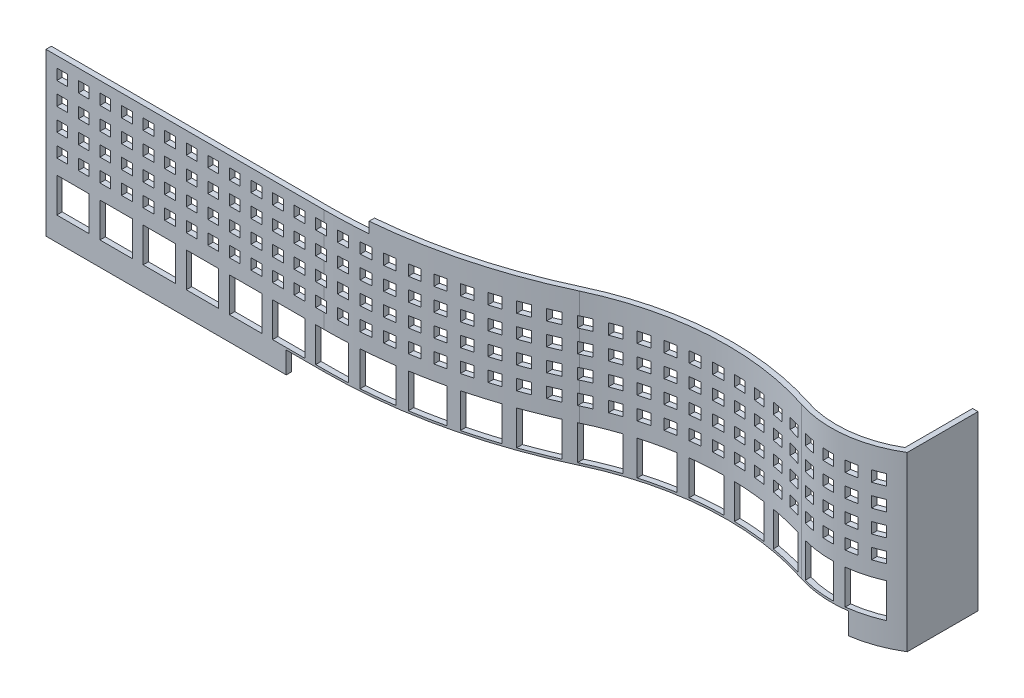
SolidWorks part; units mm, degrees
ref_plane "前视基准面" through (0, 0, 0) normal (0, 0, 1) x (1, 0, 0)
ref_plane "上视基准面" through (0, 0, 0) normal (0, 1, 0) x (1, 0, 0)
ref_plane "右视基准面" through (0, 0, 0) normal (1, 0, 0) x (0, 0, -1)
sketch "草图1" plane through (0, 0, 0) normal (0, 1, 0) x (1, 0, 0)
  line L0 (-20.7666, -25) -> (52, -25) construction
  line L1 (9, 56.2113) -> (9, -24.8219) construction
  line L2 (52, -25) -> (52, -18.6603) construction
  line L3 (52, -18.6603) -> (52, -12.3864)
  line L4 (5, -25) -> (-17.4714, -25)
  line L5 (52.5, -18.9443) -> (52.5, -12.3864)
  line L6 (5, -25.5) -> (-17.4714, -25.5)
  line L8 (52, -12.3864) -> (52.5, -12.3864)
  line L9 (-17.4714, -25) -> (-20.7666, -25)
  line L10 (-20.7666, -25) -> (-20.7666, -25.5)
  line L11 (-20.7666, -25.5) -> (-17.4714, -25.5)
  arc A0 (9, 31.229) -> (-20.7666, -25) centre (0, 0) ccw construction
  arc A1 (9, 29.1419) -> (-17.4714, -25) centre (0, 0) ccw construction
  circle A2 centre (0, 0) radius 32.5 construction
  circle A3 centre (0, 0) radius 30.5 construction
  arc A7 (43.892, -19.5048) -> (52, -18.6603) centre (47, -10) ccw
  arc A8 (43.892, -19.5048) -> (24.144, -20.7248) centre (35.5554, -45) ccw
  arc A9 (5, -25) -> (24.144, -20.7248) centre (5, 20) ccw
  arc A10 (43.7367, -19.98) -> (52.5, -18.9443) centre (47, -10) ccw
  arc A11 (43.7367, -19.98) -> (24.3567, -21.1773) centre (35.5554, -45) ccw
  arc A12 (5, -25.5) -> (24.3567, -21.1773) centre (5, 20) ccw
  dimension "D1" = 65
  dimension "D9" = 0.5
  dimension "D2" = 25
  dimension "D4" = 9
  dimension "D5" = 10
  dimension "D6" = 47
  dimension "D7" = 20
  dimension "D8" = 5
  dimension "D10" = 45
  dimension "D11" = 43
  dimension "D3" = 2
extrude "凸台-拉伸1" add sketch "草图1" along normal blind 16
sketch "草图2" plane through (0, 0, 25.5) normal (0, 0, 1) x (1, 0, 0)
  line L6 (-20.7666, 16) -> (9, 16)
  line L7 (24.3567, 16) -> (5, 16) construction
  line L8 (9, 16) -> (9, 15)
  line L9 (9, 15) -> (-20.7666, 15)
  line L10 (-20.7666, 16) -> (-20.7666, 0) construction
  line L11 (-20.7666, 15) -> (-20.7666, 16)
  dimension "D1" = 9
  dimension "D2" = 1
extrude "切除-拉伸1" cut sketch "草图2" against normal blind 15
sketch "草图3" plane through (0, 0, 0) normal (0, 0, 1) x (1, 0, 0)
  line L0 (48.2334, 14) -> (48.2334, 13)
  line L1 (-19.7666, 14) -> (-18.7666, 14)
  line L2 (-19.7666, 14) -> (-19.7666, 13)
  line L3 (-19.7666, 13) -> (-18.7666, 13)
  line L4 (-18.7666, 14) -> (-18.7666, 13)
  line L5 (48.2334, 13) -> (49.2334, 13)
  line L6 (-17.7666, 14) -> (-17.7666, 13)
  line L7 (-17.7666, 14) -> (-16.7666, 14)
  line L8 (-16.7666, 14) -> (-16.7666, 13)
  line L9 (-17.7666, 13) -> (-16.7666, 13)
  line L10 (-15.7666, 14) -> (-15.7666, 13)
  line L11 (-15.7666, 14) -> (-14.7666, 14)
  line L12 (-14.7666, 14) -> (-14.7666, 13)
  line L13 (-15.7666, 13) -> (-14.7666, 13)
  line L14 (-13.7666, 14) -> (-13.7666, 13)
  line L15 (-13.7666, 14) -> (-12.7666, 14)
  line L16 (-12.7666, 14) -> (-12.7666, 13)
  line L17 (-13.7666, 13) -> (-12.7666, 13)
  line L18 (-11.7666, 14) -> (-11.7666, 13)
  line L19 (-11.7666, 14) -> (-10.7666, 14)
  line L20 (-10.7666, 14) -> (-10.7666, 13)
  line L21 (-11.7666, 13) -> (-10.7666, 13)
  line L22 (-9.7666, 14) -> (-9.7666, 13)
  line L23 (-9.7666, 14) -> (-8.7666, 14)
  line L24 (-8.7666, 14) -> (-8.7666, 13)
  line L25 (-9.7666, 13) -> (-8.7666, 13)
  line L26 (-7.7666, 14) -> (-7.7666, 13)
  line L27 (-7.7666, 14) -> (-6.7666, 14)
  line L28 (-6.7666, 14) -> (-6.7666, 13)
  line L29 (-7.7666, 13) -> (-6.7666, 13)
  line L30 (-5.7666, 14) -> (-5.7666, 13)
  line L31 (-5.7666, 14) -> (-4.7666, 14)
  line L32 (-4.7666, 14) -> (-4.7666, 13)
  line L33 (-5.7666, 13) -> (-4.7666, 13)
  line L34 (-3.7666, 14) -> (-3.7666, 13)
  line L35 (-3.7666, 14) -> (-2.7666, 14)
  line L36 (-2.7666, 14) -> (-2.7666, 13)
  line L37 (-3.7666, 13) -> (-2.7666, 13)
  line L38 (-1.7666, 14) -> (-1.7666, 13)
  line L39 (-1.7666, 14) -> (-0.7666, 14)
  line L40 (-0.7666, 14) -> (-0.7666, 13)
  line L41 (-1.7666, 13) -> (-0.7666, 13)
  line L42 (0.2334, 14) -> (0.2334, 13)
  line L43 (0.2334, 14) -> (1.2334, 14)
  line L44 (1.2334, 14) -> (1.2334, 13)
  line L45 (0.2334, 13) -> (1.2334, 13)
  line L46 (2.2334, 14) -> (2.2334, 13)
  line L47 (2.2334, 14) -> (3.2334, 14)
  line L48 (3.2334, 14) -> (3.2334, 13)
  line L49 (2.2334, 13) -> (3.2334, 13)
  line L50 (4.2334, 14) -> (4.2334, 13)
  line L51 (4.2334, 14) -> (5.2334, 14)
  line L52 (5.2334, 14) -> (5.2334, 13)
  line L53 (4.2334, 13) -> (5.2334, 13)
  line L54 (6.2334, 14) -> (6.2334, 13)
  line L55 (6.2334, 14) -> (7.2334, 14)
  line L56 (7.2334, 14) -> (7.2334, 13)
  line L57 (6.2334, 13) -> (7.2334, 13)
  line L58 (8.2334, 14) -> (8.2334, 13)
  line L59 (8.2334, 14) -> (9.2334, 14)
  line L60 (9.2334, 14) -> (9.2334, 13)
  line L61 (8.2334, 13) -> (9.2334, 13)
  line L62 (10.2334, 14) -> (10.2334, 13)
  line L63 (10.2334, 14) -> (11.2334, 14)
  line L64 (11.2334, 14) -> (11.2334, 13)
  line L65 (10.2334, 13) -> (11.2334, 13)
  line L66 (12.2334, 14) -> (12.2334, 13)
  line L67 (12.2334, 14) -> (13.2334, 14)
  line L68 (13.2334, 14) -> (13.2334, 13)
  line L69 (12.2334, 13) -> (13.2334, 13)
  line L70 (14.2334, 14) -> (14.2334, 13)
  line L71 (14.2334, 14) -> (15.2334, 14)
  line L72 (15.2334, 14) -> (15.2334, 13)
  line L73 (14.2334, 13) -> (15.2334, 13)
  line L74 (16.2334, 14) -> (16.2334, 13)
  line L75 (16.2334, 14) -> (17.2334, 14)
  line L76 (17.2334, 14) -> (17.2334, 13)
  line L77 (16.2334, 13) -> (17.2334, 13)
  line L78 (18.2334, 14) -> (18.2334, 13)
  line L79 (18.2334, 14) -> (19.2334, 14)
  line L80 (19.2334, 14) -> (19.2334, 13)
  line L81 (18.2334, 13) -> (19.2334, 13)
  line L82 (20.2334, 14) -> (20.2334, 13)
  line L83 (20.2334, 14) -> (21.2334, 14)
  line L84 (21.2334, 14) -> (21.2334, 13)
  line L85 (20.2334, 13) -> (21.2334, 13)
  line L86 (22.2334, 14) -> (22.2334, 13)
  line L87 (22.2334, 14) -> (23.2334, 14)
  line L88 (23.2334, 14) -> (23.2334, 13)
  line L89 (22.2334, 13) -> (23.2334, 13)
  line L90 (24.2334, 14) -> (24.2334, 13)
  line L91 (24.2334, 14) -> (25.2334, 14)
  line L92 (25.2334, 14) -> (25.2334, 13)
  line L93 (24.2334, 13) -> (25.2334, 13)
  line L94 (26.2334, 14) -> (26.2334, 13)
  line L95 (26.2334, 14) -> (27.2334, 14)
  line L96 (27.2334, 14) -> (27.2334, 13)
  line L97 (26.2334, 13) -> (27.2334, 13)
  line L98 (28.2334, 14) -> (28.2334, 13)
  line L99 (28.2334, 14) -> (29.2334, 14)
  line L100 (29.2334, 14) -> (29.2334, 13)
  line L101 (28.2334, 13) -> (29.2334, 13)
  line L102 (30.2334, 14) -> (30.2334, 13)
  line L103 (30.2334, 14) -> (31.2334, 14)
  line L104 (31.2334, 14) -> (31.2334, 13)
  line L105 (30.2334, 13) -> (31.2334, 13)
  line L106 (32.2334, 14) -> (32.2334, 13)
  line L107 (32.2334, 14) -> (33.2334, 14)
  line L108 (33.2334, 14) -> (33.2334, 13)
  line L109 (32.2334, 13) -> (33.2334, 13)
  line L110 (34.2334, 14) -> (34.2334, 13)
  line L111 (34.2334, 14) -> (35.2334, 14)
  line L112 (35.2334, 14) -> (35.2334, 13)
  line L113 (34.2334, 13) -> (35.2334, 13)
  line L114 (36.2334, 14) -> (36.2334, 13)
  line L115 (36.2334, 14) -> (37.2334, 14)
  line L116 (37.2334, 14) -> (37.2334, 13)
  line L117 (36.2334, 13) -> (37.2334, 13)
  line L118 (38.2334, 14) -> (38.2334, 13)
  line L119 (38.2334, 14) -> (39.2334, 14)
  line L120 (39.2334, 14) -> (39.2334, 13)
  line L121 (38.2334, 13) -> (39.2334, 13)
  line L122 (40.2334, 14) -> (40.2334, 13)
  line L123 (40.2334, 14) -> (41.2334, 14)
  line L124 (41.2334, 14) -> (41.2334, 13)
  line L125 (40.2334, 13) -> (41.2334, 13)
  line L126 (42.2334, 14) -> (42.2334, 13)
  line L127 (42.2334, 14) -> (43.2334, 14)
  line L128 (43.2334, 14) -> (43.2334, 13)
  line L129 (42.2334, 13) -> (43.2334, 13)
  line L130 (44.2334, 14) -> (44.2334, 13)
  line L131 (44.2334, 14) -> (45.2334, 14)
  line L132 (45.2334, 14) -> (45.2334, 13)
  line L133 (44.2334, 13) -> (45.2334, 13)
  line L134 (46.2334, 14) -> (46.2334, 13)
  line L135 (46.2334, 14) -> (47.2334, 14)
  line L136 (47.2334, 14) -> (47.2334, 13)
  line L137 (46.2334, 13) -> (47.2334, 13)
  line L138 (-19.7666, 11.925) -> (-19.7666, 10.925)
  line L139 (-19.7666, 11.925) -> (-18.7666, 11.925)
  line L140 (-18.7666, 11.925) -> (-18.7666, 10.925)
  line L141 (-19.7666, 10.925) -> (-18.7666, 10.925)
  line L142 (-17.7666, 11.925) -> (-17.7666, 10.925)
  line L143 (-17.7666, 10.925) -> (-16.7666, 10.925)
  line L144 (-16.7666, 11.925) -> (-16.7666, 10.925)
  line L145 (-17.7666, 11.925) -> (-16.7666, 11.925)
  line L146 (-15.7666, 11.925) -> (-15.7666, 10.925)
  line L147 (-15.7666, 10.925) -> (-14.7666, 10.925)
  line L148 (-14.7666, 11.925) -> (-14.7666, 10.925)
  line L149 (-15.7666, 11.925) -> (-14.7666, 11.925)
  line L150 (-13.7666, 11.925) -> (-13.7666, 10.925)
  line L151 (-13.7666, 10.925) -> (-12.7666, 10.925)
  line L152 (-12.7666, 11.925) -> (-12.7666, 10.925)
  line L153 (-13.7666, 11.925) -> (-12.7666, 11.925)
  line L154 (-11.7666, 11.925) -> (-11.7666, 10.925)
  line L155 (-11.7666, 10.925) -> (-10.7666, 10.925)
  line L156 (-10.7666, 11.925) -> (-10.7666, 10.925)
  line L157 (-11.7666, 11.925) -> (-10.7666, 11.925)
  line L158 (-9.7666, 11.925) -> (-9.7666, 10.925)
  line L159 (-9.7666, 10.925) -> (-8.7666, 10.925)
  line L160 (-8.7666, 11.925) -> (-8.7666, 10.925)
  line L161 (-9.7666, 11.925) -> (-8.7666, 11.925)
  line L162 (-7.7666, 11.925) -> (-7.7666, 10.925)
  line L163 (-7.7666, 10.925) -> (-6.7666, 10.925)
  line L164 (-6.7666, 11.925) -> (-6.7666, 10.925)
  line L165 (-7.7666, 11.925) -> (-6.7666, 11.925)
  line L166 (-5.7666, 11.925) -> (-5.7666, 10.925)
  line L167 (-5.7666, 10.925) -> (-4.7666, 10.925)
  line L168 (-4.7666, 11.925) -> (-4.7666, 10.925)
  line L169 (-5.7666, 11.925) -> (-4.7666, 11.925)
  line L170 (-3.7666, 11.925) -> (-3.7666, 10.925)
  line L171 (-3.7666, 10.925) -> (-2.7666, 10.925)
  line L172 (-2.7666, 11.925) -> (-2.7666, 10.925)
  line L173 (-3.7666, 11.925) -> (-2.7666, 11.925)
  line L174 (-1.7666, 11.925) -> (-1.7666, 10.925)
  line L175 (-1.7666, 10.925) -> (-0.7666, 10.925)
  line L176 (-0.7666, 11.925) -> (-0.7666, 10.925)
  line L177 (-1.7666, 11.925) -> (-0.7666, 11.925)
  line L178 (0.2334, 11.925) -> (0.2334, 10.925)
  line L179 (0.2334, 10.925) -> (1.2334, 10.925)
  line L180 (1.2334, 11.925) -> (1.2334, 10.925)
  line L181 (0.2334, 11.925) -> (1.2334, 11.925)
  line L182 (2.2334, 11.925) -> (2.2334, 10.925)
  line L183 (2.2334, 10.925) -> (3.2334, 10.925)
  line L184 (3.2334, 11.925) -> (3.2334, 10.925)
  line L185 (2.2334, 11.925) -> (3.2334, 11.925)
  line L186 (4.2334, 11.925) -> (4.2334, 10.925)
  line L187 (4.2334, 10.925) -> (5.2334, 10.925)
  line L188 (5.2334, 11.925) -> (5.2334, 10.925)
  line L189 (4.2334, 11.925) -> (5.2334, 11.925)
  line L190 (6.2334, 11.925) -> (6.2334, 10.925)
  line L191 (6.2334, 10.925) -> (7.2334, 10.925)
  line L192 (7.2334, 11.925) -> (7.2334, 10.925)
  line L193 (6.2334, 11.925) -> (7.2334, 11.925)
  line L194 (8.2334, 11.925) -> (8.2334, 10.925)
  line L195 (8.2334, 10.925) -> (9.2334, 10.925)
  line L196 (9.2334, 11.925) -> (9.2334, 10.925)
  line L197 (8.2334, 11.925) -> (9.2334, 11.925)
  line L198 (10.2334, 11.925) -> (10.2334, 10.925)
  line L199 (10.2334, 10.925) -> (11.2334, 10.925)
  line L200 (11.2334, 11.925) -> (11.2334, 10.925)
  line L201 (10.2334, 11.925) -> (11.2334, 11.925)
  line L202 (12.2334, 11.925) -> (12.2334, 10.925)
  line L203 (12.2334, 10.925) -> (13.2334, 10.925)
  line L204 (13.2334, 11.925) -> (13.2334, 10.925)
  line L205 (12.2334, 11.925) -> (13.2334, 11.925)
  line L206 (14.2334, 11.925) -> (14.2334, 10.925)
  line L207 (14.2334, 10.925) -> (15.2334, 10.925)
  line L208 (15.2334, 11.925) -> (15.2334, 10.925)
  line L209 (14.2334, 11.925) -> (15.2334, 11.925)
  line L210 (16.2334, 11.925) -> (16.2334, 10.925)
  line L211 (16.2334, 10.925) -> (17.2334, 10.925)
  line L212 (17.2334, 11.925) -> (17.2334, 10.925)
  line L213 (16.2334, 11.925) -> (17.2334, 11.925)
  line L214 (18.2334, 11.925) -> (18.2334, 10.925)
  line L215 (18.2334, 10.925) -> (19.2334, 10.925)
  line L216 (19.2334, 11.925) -> (19.2334, 10.925)
  line L217 (18.2334, 11.925) -> (19.2334, 11.925)
  line L218 (20.2334, 11.925) -> (20.2334, 10.925)
  line L219 (20.2334, 10.925) -> (21.2334, 10.925)
  line L220 (21.2334, 11.925) -> (21.2334, 10.925)
  line L221 (20.2334, 11.925) -> (21.2334, 11.925)
  line L222 (22.2334, 11.925) -> (22.2334, 10.925)
  line L223 (22.2334, 10.925) -> (23.2334, 10.925)
  line L224 (23.2334, 11.925) -> (23.2334, 10.925)
  line L225 (22.2334, 11.925) -> (23.2334, 11.925)
  line L226 (24.2334, 11.925) -> (24.2334, 10.925)
  line L227 (24.2334, 10.925) -> (25.2334, 10.925)
  line L228 (25.2334, 11.925) -> (25.2334, 10.925)
  line L229 (24.2334, 11.925) -> (25.2334, 11.925)
  line L230 (26.2334, 11.925) -> (26.2334, 10.925)
  line L231 (26.2334, 10.925) -> (27.2334, 10.925)
  line L232 (27.2334, 11.925) -> (27.2334, 10.925)
  line L233 (26.2334, 11.925) -> (27.2334, 11.925)
  line L234 (28.2334, 11.925) -> (28.2334, 10.925)
  line L235 (28.2334, 10.925) -> (29.2334, 10.925)
  line L236 (29.2334, 11.925) -> (29.2334, 10.925)
  line L237 (28.2334, 11.925) -> (29.2334, 11.925)
  line L238 (30.2334, 11.925) -> (30.2334, 10.925)
  line L239 (30.2334, 10.925) -> (31.2334, 10.925)
  line L240 (31.2334, 11.925) -> (31.2334, 10.925)
  line L241 (30.2334, 11.925) -> (31.2334, 11.925)
  line L242 (32.2334, 11.925) -> (32.2334, 10.925)
  line L243 (32.2334, 10.925) -> (33.2334, 10.925)
  line L244 (33.2334, 11.925) -> (33.2334, 10.925)
  line L245 (32.2334, 11.925) -> (33.2334, 11.925)
  line L246 (34.2334, 11.925) -> (34.2334, 10.925)
  line L247 (34.2334, 10.925) -> (35.2334, 10.925)
  line L248 (35.2334, 11.925) -> (35.2334, 10.925)
  line L249 (34.2334, 11.925) -> (35.2334, 11.925)
  line L250 (36.2334, 11.925) -> (36.2334, 10.925)
  line L251 (36.2334, 10.925) -> (37.2334, 10.925)
  line L252 (37.2334, 11.925) -> (37.2334, 10.925)
  line L253 (36.2334, 11.925) -> (37.2334, 11.925)
  line L254 (38.2334, 11.925) -> (38.2334, 10.925)
  line L255 (38.2334, 10.925) -> (39.2334, 10.925)
  line L256 (39.2334, 11.925) -> (39.2334, 10.925)
  line L257 (38.2334, 11.925) -> (39.2334, 11.925)
  line L258 (40.2334, 11.925) -> (40.2334, 10.925)
  line L259 (40.2334, 10.925) -> (41.2334, 10.925)
  line L260 (41.2334, 11.925) -> (41.2334, 10.925)
  line L261 (40.2334, 11.925) -> (41.2334, 11.925)
  line L262 (42.2334, 11.925) -> (42.2334, 10.925)
  line L263 (42.2334, 10.925) -> (43.2334, 10.925)
  line L264 (43.2334, 11.925) -> (43.2334, 10.925)
  line L265 (42.2334, 11.925) -> (43.2334, 11.925)
  line L266 (44.2334, 11.925) -> (44.2334, 10.925)
  line L267 (44.2334, 10.925) -> (45.2334, 10.925)
  line L268 (45.2334, 11.925) -> (45.2334, 10.925)
  line L269 (44.2334, 11.925) -> (45.2334, 11.925)
  line L270 (46.2334, 11.925) -> (46.2334, 10.925)
  line L271 (46.2334, 10.925) -> (47.2334, 10.925)
  line L272 (47.2334, 11.925) -> (47.2334, 10.925)
  line L273 (46.2334, 11.925) -> (47.2334, 11.925)
  line L274 (-19.7666, 9.85) -> (-19.7666, 8.85)
  line L275 (-19.7666, 9.85) -> (-18.7666, 9.85)
  line L276 (-18.7666, 9.85) -> (-18.7666, 8.85)
  line L277 (-19.7666, 8.85) -> (-18.7666, 8.85)
  line L278 (-17.7666, 9.85) -> (-17.7666, 8.85)
  line L279 (-17.7666, 8.85) -> (-16.7666, 8.85)
  line L280 (-16.7666, 9.85) -> (-16.7666, 8.85)
  line L281 (-17.7666, 9.85) -> (-16.7666, 9.85)
  line L282 (-15.7666, 9.85) -> (-15.7666, 8.85)
  line L283 (-15.7666, 8.85) -> (-14.7666, 8.85)
  line L284 (-14.7666, 9.85) -> (-14.7666, 8.85)
  line L285 (-15.7666, 9.85) -> (-14.7666, 9.85)
  line L286 (-13.7666, 9.85) -> (-13.7666, 8.85)
  line L287 (-13.7666, 8.85) -> (-12.7666, 8.85)
  line L288 (-12.7666, 9.85) -> (-12.7666, 8.85)
  line L289 (-13.7666, 9.85) -> (-12.7666, 9.85)
  line L290 (-11.7666, 9.85) -> (-11.7666, 8.85)
  line L291 (-11.7666, 8.85) -> (-10.7666, 8.85)
  line L292 (-10.7666, 9.85) -> (-10.7666, 8.85)
  line L293 (-11.7666, 9.85) -> (-10.7666, 9.85)
  line L294 (-9.7666, 9.85) -> (-9.7666, 8.85)
  line L295 (-9.7666, 8.85) -> (-8.7666, 8.85)
  line L296 (-8.7666, 9.85) -> (-8.7666, 8.85)
  line L297 (-9.7666, 9.85) -> (-8.7666, 9.85)
  line L298 (-7.7666, 9.85) -> (-7.7666, 8.85)
  line L299 (-7.7666, 8.85) -> (-6.7666, 8.85)
  line L300 (-6.7666, 9.85) -> (-6.7666, 8.85)
  line L301 (-7.7666, 9.85) -> (-6.7666, 9.85)
  line L302 (-5.7666, 9.85) -> (-5.7666, 8.85)
  line L303 (-5.7666, 8.85) -> (-4.7666, 8.85)
  line L304 (-4.7666, 9.85) -> (-4.7666, 8.85)
  line L305 (-5.7666, 9.85) -> (-4.7666, 9.85)
  line L306 (-3.7666, 9.85) -> (-3.7666, 8.85)
  line L307 (-3.7666, 8.85) -> (-2.7666, 8.85)
  line L308 (-2.7666, 9.85) -> (-2.7666, 8.85)
  line L309 (-3.7666, 9.85) -> (-2.7666, 9.85)
  line L310 (-1.7666, 9.85) -> (-1.7666, 8.85)
  line L311 (-1.7666, 8.85) -> (-0.7666, 8.85)
  line L312 (-0.7666, 9.85) -> (-0.7666, 8.85)
  line L313 (-1.7666, 9.85) -> (-0.7666, 9.85)
  line L314 (0.2334, 9.85) -> (0.2334, 8.85)
  line L315 (0.2334, 8.85) -> (1.2334, 8.85)
  line L316 (1.2334, 9.85) -> (1.2334, 8.85)
  line L317 (0.2334, 9.85) -> (1.2334, 9.85)
  line L318 (2.2334, 9.85) -> (2.2334, 8.85)
  line L319 (2.2334, 8.85) -> (3.2334, 8.85)
  line L320 (3.2334, 9.85) -> (3.2334, 8.85)
  line L321 (2.2334, 9.85) -> (3.2334, 9.85)
  line L322 (4.2334, 9.85) -> (4.2334, 8.85)
  line L323 (4.2334, 8.85) -> (5.2334, 8.85)
  line L324 (5.2334, 9.85) -> (5.2334, 8.85)
  line L325 (4.2334, 9.85) -> (5.2334, 9.85)
  line L326 (6.2334, 9.85) -> (6.2334, 8.85)
  line L327 (6.2334, 8.85) -> (7.2334, 8.85)
  line L328 (7.2334, 9.85) -> (7.2334, 8.85)
  line L329 (6.2334, 9.85) -> (7.2334, 9.85)
  line L330 (8.2334, 9.85) -> (8.2334, 8.85)
  line L331 (8.2334, 8.85) -> (9.2334, 8.85)
  line L332 (9.2334, 9.85) -> (9.2334, 8.85)
  line L333 (8.2334, 9.85) -> (9.2334, 9.85)
  line L334 (10.2334, 9.85) -> (10.2334, 8.85)
  line L335 (10.2334, 8.85) -> (11.2334, 8.85)
  line L336 (11.2334, 9.85) -> (11.2334, 8.85)
  line L337 (10.2334, 9.85) -> (11.2334, 9.85)
  line L338 (12.2334, 9.85) -> (12.2334, 8.85)
  line L339 (12.2334, 8.85) -> (13.2334, 8.85)
  line L340 (13.2334, 9.85) -> (13.2334, 8.85)
  line L341 (12.2334, 9.85) -> (13.2334, 9.85)
  line L342 (14.2334, 9.85) -> (14.2334, 8.85)
  line L343 (14.2334, 8.85) -> (15.2334, 8.85)
  line L344 (15.2334, 9.85) -> (15.2334, 8.85)
  line L345 (14.2334, 9.85) -> (15.2334, 9.85)
  line L346 (16.2334, 9.85) -> (16.2334, 8.85)
  line L347 (16.2334, 8.85) -> (17.2334, 8.85)
  line L348 (17.2334, 9.85) -> (17.2334, 8.85)
  line L349 (16.2334, 9.85) -> (17.2334, 9.85)
  line L350 (18.2334, 9.85) -> (18.2334, 8.85)
  line L351 (18.2334, 8.85) -> (19.2334, 8.85)
  line L352 (19.2334, 9.85) -> (19.2334, 8.85)
  line L353 (18.2334, 9.85) -> (19.2334, 9.85)
  line L354 (20.2334, 9.85) -> (20.2334, 8.85)
  line L355 (20.2334, 8.85) -> (21.2334, 8.85)
  line L356 (21.2334, 9.85) -> (21.2334, 8.85)
  line L357 (20.2334, 9.85) -> (21.2334, 9.85)
  line L358 (22.2334, 9.85) -> (22.2334, 8.85)
  line L359 (22.2334, 8.85) -> (23.2334, 8.85)
  line L360 (23.2334, 9.85) -> (23.2334, 8.85)
  line L361 (22.2334, 9.85) -> (23.2334, 9.85)
  line L362 (24.2334, 9.85) -> (24.2334, 8.85)
  line L363 (24.2334, 8.85) -> (25.2334, 8.85)
  line L364 (25.2334, 9.85) -> (25.2334, 8.85)
  line L365 (24.2334, 9.85) -> (25.2334, 9.85)
  line L366 (26.2334, 9.85) -> (26.2334, 8.85)
  line L367 (26.2334, 8.85) -> (27.2334, 8.85)
  line L368 (27.2334, 9.85) -> (27.2334, 8.85)
  line L369 (26.2334, 9.85) -> (27.2334, 9.85)
  line L370 (28.2334, 9.85) -> (28.2334, 8.85)
  line L371 (28.2334, 8.85) -> (29.2334, 8.85)
  line L372 (29.2334, 9.85) -> (29.2334, 8.85)
  line L373 (28.2334, 9.85) -> (29.2334, 9.85)
  line L374 (30.2334, 9.85) -> (30.2334, 8.85)
  line L375 (30.2334, 8.85) -> (31.2334, 8.85)
  line L376 (31.2334, 9.85) -> (31.2334, 8.85)
  line L377 (30.2334, 9.85) -> (31.2334, 9.85)
  line L378 (32.2334, 9.85) -> (32.2334, 8.85)
  line L379 (32.2334, 8.85) -> (33.2334, 8.85)
  line L380 (33.2334, 9.85) -> (33.2334, 8.85)
  line L381 (32.2334, 9.85) -> (33.2334, 9.85)
  line L382 (34.2334, 9.85) -> (34.2334, 8.85)
  line L383 (34.2334, 8.85) -> (35.2334, 8.85)
  line L384 (35.2334, 9.85) -> (35.2334, 8.85)
  line L385 (34.2334, 9.85) -> (35.2334, 9.85)
  line L386 (36.2334, 9.85) -> (36.2334, 8.85)
  line L387 (36.2334, 8.85) -> (37.2334, 8.85)
  line L388 (37.2334, 9.85) -> (37.2334, 8.85)
  line L389 (36.2334, 9.85) -> (37.2334, 9.85)
  line L390 (38.2334, 9.85) -> (38.2334, 8.85)
  line L391 (38.2334, 8.85) -> (39.2334, 8.85)
  line L392 (39.2334, 9.85) -> (39.2334, 8.85)
  line L393 (38.2334, 9.85) -> (39.2334, 9.85)
  line L394 (40.2334, 9.85) -> (40.2334, 8.85)
  line L395 (40.2334, 8.85) -> (41.2334, 8.85)
  line L396 (41.2334, 9.85) -> (41.2334, 8.85)
  line L397 (40.2334, 9.85) -> (41.2334, 9.85)
  line L398 (42.2334, 9.85) -> (42.2334, 8.85)
  line L399 (42.2334, 8.85) -> (43.2334, 8.85)
  line L400 (43.2334, 9.85) -> (43.2334, 8.85)
  line L401 (42.2334, 9.85) -> (43.2334, 9.85)
  line L402 (44.2334, 9.85) -> (44.2334, 8.85)
  line L403 (44.2334, 8.85) -> (45.2334, 8.85)
  line L404 (45.2334, 9.85) -> (45.2334, 8.85)
  line L405 (44.2334, 9.85) -> (45.2334, 9.85)
  line L406 (46.2334, 9.85) -> (46.2334, 8.85)
  line L407 (46.2334, 8.85) -> (47.2334, 8.85)
  line L408 (47.2334, 9.85) -> (47.2334, 8.85)
  line L409 (46.2334, 9.85) -> (47.2334, 9.85)
  line L410 (-19.7666, 7.775) -> (-19.7666, 6.775)
  line L411 (-19.7666, 7.775) -> (-18.7666, 7.775)
  line L412 (-18.7666, 7.775) -> (-18.7666, 6.775)
  line L413 (-19.7666, 6.775) -> (-18.7666, 6.775)
  line L414 (-17.7666, 7.775) -> (-17.7666, 6.775)
  line L415 (-17.7666, 6.775) -> (-16.7666, 6.775)
  line L416 (-16.7666, 7.775) -> (-16.7666, 6.775)
  line L417 (-17.7666, 7.775) -> (-16.7666, 7.775)
  line L418 (-15.7666, 7.775) -> (-15.7666, 6.775)
  line L419 (-15.7666, 6.775) -> (-14.7666, 6.775)
  line L420 (-14.7666, 7.775) -> (-14.7666, 6.775)
  line L421 (-15.7666, 7.775) -> (-14.7666, 7.775)
  line L422 (-13.7666, 7.775) -> (-13.7666, 6.775)
  line L423 (-13.7666, 6.775) -> (-12.7666, 6.775)
  line L424 (-12.7666, 7.775) -> (-12.7666, 6.775)
  line L425 (-13.7666, 7.775) -> (-12.7666, 7.775)
  line L426 (-11.7666, 7.775) -> (-11.7666, 6.775)
  line L427 (-11.7666, 6.775) -> (-10.7666, 6.775)
  line L428 (-10.7666, 7.775) -> (-10.7666, 6.775)
  line L429 (-11.7666, 7.775) -> (-10.7666, 7.775)
  line L430 (-9.7666, 7.775) -> (-9.7666, 6.775)
  line L431 (-9.7666, 6.775) -> (-8.7666, 6.775)
  line L432 (-8.7666, 7.775) -> (-8.7666, 6.775)
  line L433 (-9.7666, 7.775) -> (-8.7666, 7.775)
  line L434 (-7.7666, 7.775) -> (-7.7666, 6.775)
  line L435 (-7.7666, 6.775) -> (-6.7666, 6.775)
  line L436 (-6.7666, 7.775) -> (-6.7666, 6.775)
  line L437 (-7.7666, 7.775) -> (-6.7666, 7.775)
  line L438 (-5.7666, 7.775) -> (-5.7666, 6.775)
  line L439 (-5.7666, 6.775) -> (-4.7666, 6.775)
  line L440 (-4.7666, 7.775) -> (-4.7666, 6.775)
  line L441 (-5.7666, 7.775) -> (-4.7666, 7.775)
  line L442 (-3.7666, 7.775) -> (-3.7666, 6.775)
  line L443 (-3.7666, 6.775) -> (-2.7666, 6.775)
  line L444 (-2.7666, 7.775) -> (-2.7666, 6.775)
  line L445 (-3.7666, 7.775) -> (-2.7666, 7.775)
  line L446 (-1.7666, 7.775) -> (-1.7666, 6.775)
  line L447 (-1.7666, 6.775) -> (-0.7666, 6.775)
  line L448 (-0.7666, 7.775) -> (-0.7666, 6.775)
  line L449 (-1.7666, 7.775) -> (-0.7666, 7.775)
  line L450 (0.2334, 7.775) -> (0.2334, 6.775)
  line L451 (0.2334, 6.775) -> (1.2334, 6.775)
  line L452 (1.2334, 7.775) -> (1.2334, 6.775)
  line L453 (0.2334, 7.775) -> (1.2334, 7.775)
  line L454 (2.2334, 7.775) -> (2.2334, 6.775)
  line L455 (2.2334, 6.775) -> (3.2334, 6.775)
  line L456 (3.2334, 7.775) -> (3.2334, 6.775)
  line L457 (2.2334, 7.775) -> (3.2334, 7.775)
  line L458 (4.2334, 7.775) -> (4.2334, 6.775)
  line L459 (4.2334, 6.775) -> (5.2334, 6.775)
  line L460 (5.2334, 7.775) -> (5.2334, 6.775)
  line L461 (4.2334, 7.775) -> (5.2334, 7.775)
  line L462 (6.2334, 7.775) -> (6.2334, 6.775)
  line L463 (6.2334, 6.775) -> (7.2334, 6.775)
  line L464 (7.2334, 7.775) -> (7.2334, 6.775)
  line L465 (6.2334, 7.775) -> (7.2334, 7.775)
  line L466 (8.2334, 7.775) -> (8.2334, 6.775)
  line L467 (8.2334, 6.775) -> (9.2334, 6.775)
  line L468 (9.2334, 7.775) -> (9.2334, 6.775)
  line L469 (8.2334, 7.775) -> (9.2334, 7.775)
  line L470 (10.2334, 7.775) -> (10.2334, 6.775)
  line L471 (10.2334, 6.775) -> (11.2334, 6.775)
  line L472 (11.2334, 7.775) -> (11.2334, 6.775)
  line L473 (10.2334, 7.775) -> (11.2334, 7.775)
  line L474 (12.2334, 7.775) -> (12.2334, 6.775)
  line L475 (12.2334, 6.775) -> (13.2334, 6.775)
  line L476 (13.2334, 7.775) -> (13.2334, 6.775)
  line L477 (12.2334, 7.775) -> (13.2334, 7.775)
  line L478 (14.2334, 7.775) -> (14.2334, 6.775)
  line L479 (14.2334, 6.775) -> (15.2334, 6.775)
  line L480 (15.2334, 7.775) -> (15.2334, 6.775)
  line L481 (14.2334, 7.775) -> (15.2334, 7.775)
  line L482 (16.2334, 7.775) -> (16.2334, 6.775)
  line L483 (16.2334, 6.775) -> (17.2334, 6.775)
  line L484 (17.2334, 7.775) -> (17.2334, 6.775)
  line L485 (16.2334, 7.775) -> (17.2334, 7.775)
  line L486 (18.2334, 7.775) -> (18.2334, 6.775)
  line L487 (18.2334, 6.775) -> (19.2334, 6.775)
  line L488 (19.2334, 7.775) -> (19.2334, 6.775)
  line L489 (18.2334, 7.775) -> (19.2334, 7.775)
  line L490 (20.2334, 7.775) -> (20.2334, 6.775)
  line L491 (20.2334, 6.775) -> (21.2334, 6.775)
  line L492 (21.2334, 7.775) -> (21.2334, 6.775)
  line L493 (20.2334, 7.775) -> (21.2334, 7.775)
  line L494 (22.2334, 7.775) -> (22.2334, 6.775)
  line L495 (22.2334, 6.775) -> (23.2334, 6.775)
  line L496 (23.2334, 7.775) -> (23.2334, 6.775)
  line L497 (22.2334, 7.775) -> (23.2334, 7.775)
  line L498 (24.2334, 7.775) -> (24.2334, 6.775)
  line L499 (24.2334, 6.775) -> (25.2334, 6.775)
  line L500 (25.2334, 7.775) -> (25.2334, 6.775)
  line L501 (24.2334, 7.775) -> (25.2334, 7.775)
  line L502 (26.2334, 7.775) -> (26.2334, 6.775)
  line L503 (26.2334, 6.775) -> (27.2334, 6.775)
  line L504 (27.2334, 7.775) -> (27.2334, 6.775)
  line L505 (26.2334, 7.775) -> (27.2334, 7.775)
  line L506 (28.2334, 7.775) -> (28.2334, 6.775)
  line L507 (28.2334, 6.775) -> (29.2334, 6.775)
  line L508 (29.2334, 7.775) -> (29.2334, 6.775)
  line L509 (28.2334, 7.775) -> (29.2334, 7.775)
  line L510 (30.2334, 7.775) -> (30.2334, 6.775)
  line L511 (30.2334, 6.775) -> (31.2334, 6.775)
  line L512 (31.2334, 7.775) -> (31.2334, 6.775)
  line L513 (30.2334, 7.775) -> (31.2334, 7.775)
  line L514 (32.2334, 7.775) -> (32.2334, 6.775)
  line L515 (32.2334, 6.775) -> (33.2334, 6.775)
  line L516 (33.2334, 7.775) -> (33.2334, 6.775)
  line L517 (32.2334, 7.775) -> (33.2334, 7.775)
  line L518 (34.2334, 7.775) -> (34.2334, 6.775)
  line L519 (34.2334, 6.775) -> (35.2334, 6.775)
  line L520 (35.2334, 7.775) -> (35.2334, 6.775)
  line L521 (34.2334, 7.775) -> (35.2334, 7.775)
  line L522 (36.2334, 7.775) -> (36.2334, 6.775)
  line L523 (36.2334, 6.775) -> (37.2334, 6.775)
  line L524 (37.2334, 7.775) -> (37.2334, 6.775)
  line L525 (36.2334, 7.775) -> (37.2334, 7.775)
  line L526 (38.2334, 7.775) -> (38.2334, 6.775)
  line L527 (38.2334, 6.775) -> (39.2334, 6.775)
  line L528 (39.2334, 7.775) -> (39.2334, 6.775)
  line L529 (38.2334, 7.775) -> (39.2334, 7.775)
  line L530 (40.2334, 7.775) -> (40.2334, 6.775)
  line L531 (40.2334, 6.775) -> (41.2334, 6.775)
  line L532 (41.2334, 7.775) -> (41.2334, 6.775)
  line L533 (40.2334, 7.775) -> (41.2334, 7.775)
  line L534 (42.2334, 7.775) -> (42.2334, 6.775)
  line L535 (42.2334, 6.775) -> (43.2334, 6.775)
  line L536 (43.2334, 7.775) -> (43.2334, 6.775)
  line L537 (42.2334, 7.775) -> (43.2334, 7.775)
  line L538 (44.2334, 7.775) -> (44.2334, 6.775)
  line L539 (44.2334, 6.775) -> (45.2334, 6.775)
  line L540 (45.2334, 7.775) -> (45.2334, 6.775)
  line L541 (44.2334, 7.775) -> (45.2334, 7.775)
  line L542 (46.2334, 7.775) -> (46.2334, 6.775)
  line L543 (46.2334, 6.775) -> (47.2334, 6.775)
  line L544 (47.2334, 7.775) -> (47.2334, 6.775)
  line L545 (46.2334, 7.775) -> (47.2334, 7.775)
  line L682 (-20.7666, 0) -> (5, 0) construction
  line L683 (-19.7666, 5.4) -> (-16.7666, 5.4)
  line L684 (-19.7666, 5.4) -> (-19.7666, 2.2)
  line L685 (-19.7666, 2.2) -> (-16.7666, 2.2)
  line L686 (-16.7666, 5.4) -> (-16.7666, 2.2)
  line L687 (-15.7666, 5.4) -> (-15.7666, 2.2)
  line L688 (-15.7666, 5.4) -> (-12.7666, 5.4)
  line L689 (-12.7666, 5.4) -> (-12.7666, 2.2)
  line L690 (-15.7666, 2.2) -> (-12.7666, 2.2)
  line L691 (-11.7666, 5.4) -> (-11.7666, 2.2)
  line L692 (-11.7666, 5.4) -> (-8.7666, 5.4)
  line L693 (-8.7666, 5.4) -> (-8.7666, 2.2)
  line L694 (-11.7666, 2.2) -> (-8.7666, 2.2)
  line L695 (-7.7666, 5.4) -> (-7.7666, 2.2)
  line L696 (-7.7666, 5.4) -> (-4.7666, 5.4)
  line L697 (-4.7666, 5.4) -> (-4.7666, 2.2)
  line L698 (-7.7666, 2.2) -> (-4.7666, 2.2)
  line L699 (-3.7666, 5.4) -> (-3.7666, 2.2)
  line L700 (-3.7666, 5.4) -> (-0.7666, 5.4)
  line L701 (-0.7666, 5.4) -> (-0.7666, 2.2)
  line L702 (-3.7666, 2.2) -> (-0.7666, 2.2)
  line L703 (0.2334, 5.4) -> (0.2334, 2.2)
  line L704 (0.2334, 5.4) -> (3.2334, 5.4)
  line L705 (3.2334, 5.4) -> (3.2334, 2.2)
  line L706 (0.2334, 2.2) -> (3.2334, 2.2)
  line L707 (4.2334, 5.4) -> (4.2334, 2.2)
  line L708 (4.2334, 5.4) -> (7.2334, 5.4)
  line L709 (7.2334, 5.4) -> (7.2334, 2.2)
  line L710 (4.2334, 2.2) -> (7.2334, 2.2)
  line L711 (8.2334, 5.4) -> (8.2334, 2.2)
  line L712 (8.2334, 5.4) -> (11.2334, 5.4)
  line L713 (11.2334, 5.4) -> (11.2334, 2.2)
  line L714 (8.2334, 2.2) -> (11.2334, 2.2)
  line L715 (12.2334, 5.4) -> (12.2334, 2.2)
  line L716 (12.2334, 5.4) -> (15.2334, 5.4)
  line L717 (15.2334, 5.4) -> (15.2334, 2.2)
  line L718 (12.2334, 2.2) -> (15.2334, 2.2)
  line L719 (16.2334, 5.4) -> (16.2334, 2.2)
  line L720 (16.2334, 5.4) -> (19.2334, 5.4)
  line L721 (19.2334, 5.4) -> (19.2334, 2.2)
  line L722 (16.2334, 2.2) -> (19.2334, 2.2)
  line L723 (20.2334, 5.4) -> (20.2334, 2.2)
  line L724 (20.2334, 5.4) -> (23.2334, 5.4)
  line L725 (23.2334, 5.4) -> (23.2334, 2.2)
  line L726 (20.2334, 2.2) -> (23.2334, 2.2)
  line L727 (24.2334, 5.4) -> (24.2334, 2.2)
  line L728 (24.2334, 5.4) -> (27.2334, 5.4)
  line L729 (27.2334, 5.4) -> (27.2334, 2.2)
  line L730 (24.2334, 2.2) -> (27.2334, 2.2)
  line L731 (28.2334, 5.4) -> (28.2334, 2.2)
  line L732 (28.2334, 5.4) -> (31.2334, 5.4)
  line L733 (31.2334, 5.4) -> (31.2334, 2.2)
  line L734 (28.2334, 2.2) -> (31.2334, 2.2)
  line L735 (32.2334, 5.4) -> (32.2334, 2.2)
  line L736 (32.2334, 5.4) -> (35.2334, 5.4)
  line L737 (35.2334, 5.4) -> (35.2334, 2.2)
  line L738 (32.2334, 2.2) -> (35.2334, 2.2)
  line L739 (36.2334, 5.4) -> (36.2334, 2.2)
  line L740 (36.2334, 5.4) -> (39.2334, 5.4)
  line L741 (39.2334, 5.4) -> (39.2334, 2.2)
  line L742 (36.2334, 2.2) -> (39.2334, 2.2)
  line L743 (40.2334, 5.4) -> (40.2334, 2.2)
  line L744 (40.2334, 5.4) -> (43.2334, 5.4)
  line L745 (43.2334, 5.4) -> (43.2334, 2.2)
  line L746 (40.2334, 2.2) -> (43.2334, 2.2)
  line L747 (44.2334, 5.4) -> (44.2334, 2.2)
  line L748 (44.2334, 5.4) -> (47.2334, 5.4)
  line L749 (47.2334, 5.4) -> (47.2334, 2.2)
  line L750 (44.2334, 2.2) -> (47.2334, 2.2)
  line L751 (-20.7666, 15) -> (-20.7666, 0) construction
  line L752 (-20.7666, 15) -> (5, 15) construction
  line L753 (-19.7666, 5.7) -> (-19.7666, 4.7) [skipped]
  line L754 (-18.7666, 5.7) -> (-18.7666, 4.7) [skipped]
  line L755 (-17.7666, 5.7) -> (-17.7666, 4.7) [skipped]
  line L756 (-16.7666, 5.7) -> (-16.7666, 4.7) [skipped]
  line L757 (-15.7666, 5.7) -> (-15.7666, 4.7) [skipped]
  line L758 (-14.7666, 5.7) -> (-14.7666, 4.7) [skipped]
  line L759 (-13.7666, 5.7) -> (-13.7666, 4.7) [skipped]
  line L760 (-12.7666, 5.7) -> (-12.7666, 4.7) [skipped]
  line L761 (-11.7666, 5.7) -> (-11.7666, 4.7) [skipped]
  line L762 (-10.7666, 5.7) -> (-10.7666, 4.7) [skipped]
  line L763 (-9.7666, 5.7) -> (-9.7666, 4.7) [skipped]
  line L764 (-8.7666, 5.7) -> (-8.7666, 4.7) [skipped]
  line L765 (-7.7666, 5.7) -> (-7.7666, 4.7) [skipped]
  line L766 (-6.7666, 5.7) -> (-6.7666, 4.7) [skipped]
  line L767 (-5.7666, 5.7) -> (-5.7666, 4.7) [skipped]
  line L768 (-4.7666, 5.7) -> (-4.7666, 4.7) [skipped]
  line L769 (-3.7666, 5.7) -> (-3.7666, 4.7) [skipped]
  line L770 (-2.7666, 5.7) -> (-2.7666, 4.7) [skipped]
  line L771 (-1.7666, 5.7) -> (-1.7666, 4.7) [skipped]
  line L772 (-0.7666, 5.7) -> (-0.7666, 4.7) [skipped]
  line L773 (0.2334, 5.7) -> (0.2334, 4.7) [skipped]
  line L774 (1.2334, 5.7) -> (1.2334, 4.7) [skipped]
  line L775 (2.2334, 5.7) -> (2.2334, 4.7) [skipped]
  line L776 (3.2334, 5.7) -> (3.2334, 4.7) [skipped]
  line L777 (4.2334, 5.7) -> (4.2334, 4.7) [skipped]
  line L778 (5.2334, 5.7) -> (5.2334, 4.7) [skipped]
  line L779 (6.2334, 5.7) -> (6.2334, 4.7) [skipped]
  line L780 (7.2334, 5.7) -> (7.2334, 4.7) [skipped]
  line L781 (8.2334, 5.7) -> (8.2334, 4.7) [skipped]
  line L782 (9.2334, 5.7) -> (9.2334, 4.7) [skipped]
  line L783 (10.2334, 5.7) -> (10.2334, 4.7) [skipped]
  line L784 (11.2334, 5.7) -> (11.2334, 4.7) [skipped]
  line L785 (12.2334, 5.7) -> (12.2334, 4.7) [skipped]
  line L786 (13.2334, 5.7) -> (13.2334, 4.7) [skipped]
  line L787 (14.2334, 5.7) -> (14.2334, 4.7) [skipped]
  line L788 (15.2334, 5.7) -> (15.2334, 4.7) [skipped]
  line L789 (16.2334, 5.7) -> (16.2334, 4.7) [skipped]
  line L790 (17.2334, 5.7) -> (17.2334, 4.7) [skipped]
  line L791 (18.2334, 5.7) -> (18.2334, 4.7) [skipped]
  line L792 (19.2334, 5.7) -> (19.2334, 4.7) [skipped]
  line L793 (20.2334, 5.7) -> (20.2334, 4.7) [skipped]
  line L794 (21.2334, 5.7) -> (21.2334, 4.7) [skipped]
  line L795 (22.2334, 5.7) -> (22.2334, 4.7) [skipped]
  line L796 (23.2334, 5.7) -> (23.2334, 4.7) [skipped]
  line L797 (24.2334, 5.7) -> (24.2334, 4.7) [skipped]
  line L798 (25.2334, 5.7) -> (25.2334, 4.7) [skipped]
  line L799 (26.2334, 5.7) -> (26.2334, 4.7) [skipped]
  line L800 (27.2334, 5.7) -> (27.2334, 4.7) [skipped]
  line L801 (28.2334, 5.7) -> (28.2334, 4.7) [skipped]
  line L802 (29.2334, 5.7) -> (29.2334, 4.7) [skipped]
  line L803 (30.2334, 5.7) -> (30.2334, 4.7) [skipped]
  line L804 (31.2334, 5.7) -> (31.2334, 4.7) [skipped]
  line L805 (32.2334, 5.7) -> (32.2334, 4.7) [skipped]
  line L806 (33.2334, 5.7) -> (33.2334, 4.7) [skipped]
  line L807 (34.2334, 5.7) -> (34.2334, 4.7) [skipped]
  line L808 (35.2334, 5.7) -> (35.2334, 4.7) [skipped]
  line L809 (36.2334, 5.7) -> (36.2334, 4.7) [skipped]
  line L810 (37.2334, 5.7) -> (37.2334, 4.7) [skipped]
  line L811 (38.2334, 5.7) -> (38.2334, 4.7) [skipped]
  line L812 (39.2334, 5.7) -> (39.2334, 4.7) [skipped]
  line L813 (40.2334, 5.7) -> (40.2334, 4.7) [skipped]
  line L814 (41.2334, 5.7) -> (41.2334, 4.7) [skipped]
  line L815 (42.2334, 5.7) -> (42.2334, 4.7) [skipped]
  line L816 (43.2334, 5.7) -> (43.2334, 4.7) [skipped]
  line L817 (44.2334, 5.7) -> (44.2334, 4.7) [skipped]
  line L818 (45.2334, 5.7) -> (45.2334, 4.7) [skipped]
  line L819 (46.2334, 5.7) -> (46.2334, 4.7) [skipped]
  line L820 (47.2334, 5.7) -> (47.2334, 4.7) [skipped]
  line L821 (46.2334, 5.7) -> (47.2334, 5.7) [skipped]
  line L822 (46.2334, 4.7) -> (47.2334, 4.7) [skipped]
  line L823 (44.2334, 4.7) -> (45.2334, 4.7) [skipped]
  line L824 (44.2334, 5.7) -> (45.2334, 5.7) [skipped]
  line L825 (42.2334, 4.7) -> (42.719, 4.7) [skipped]
  line L826 (42.2334, 5.7) -> (43.2334, 5.7) [skipped]
  line L827 (40.2334, 5.7) -> (41.2334, 5.7) [skipped]
  line L828 (40.2334, 4.7) -> (41.2334, 4.7) [skipped]
  line L829 (38.2334, 4.7) -> (39.2334, 4.7) [skipped]
  line L830 (38.2334, 5.7) -> (39.2334, 5.7) [skipped]
  line L831 (36.2334, 5.7) -> (37.2334, 5.7) [skipped]
  line L832 (36.2334, 4.7) -> (37.2334, 4.7) [skipped]
  line L833 (34.2334, 4.7) -> (35.2334, 4.7) [skipped]
  line L834 (34.2334, 5.7) -> (35.2334, 5.7) [skipped]
  line L835 (32.2334, 5.7) -> (33.2334, 5.7) [skipped]
  line L836 (32.2334, 4.7) -> (33.2334, 4.7) [skipped]
  line L837 (30.2334, 4.7) -> (31.2334, 4.7) [skipped]
  line L838 (30.2334, 5.7) -> (31.2334, 5.7) [skipped]
  line L839 (28.2334, 5.7) -> (29.2334, 5.7) [skipped]
  line L840 (28.2334, 4.7) -> (29.2334, 4.7) [skipped]
  line L841 (26.2334, 4.7) -> (27.2334, 4.7) [skipped]
  line L842 (26.2334, 5.7) -> (27.2334, 5.7) [skipped]
  line L843 (24.2334, 5.7) -> (25.2334, 5.7) [skipped]
  line L844 (24.2334, 4.7) -> (25.2334, 4.7) [skipped]
  line L845 (22.2334, 4.7) -> (23.2334, 4.7) [skipped]
  line L846 (22.2334, 5.7) -> (23.2334, 5.7) [skipped]
  line L847 (20.2334, 5.7) -> (21.2334, 5.7) [skipped]
  line L848 (20.2334, 4.7) -> (21.2334, 4.7) [skipped]
  line L849 (18.2334, 4.7) -> (19.2334, 4.7) [skipped]
  line L850 (18.2334, 5.7) -> (19.2334, 5.7) [skipped]
  line L851 (16.2334, 5.7) -> (17.2334, 5.7) [skipped]
  line L852 (16.2334, 4.7) -> (17.2334, 4.7) [skipped]
  line L853 (14.2334, 4.7) -> (15.2334, 4.7) [skipped]
  line L854 (14.2334, 5.7) -> (15.2334, 5.7) [skipped]
  line L855 (12.2334, 4.7) -> (13.2334, 4.7) [skipped]
  line L856 (12.2334, 5.7) -> (13.2334, 5.7) [skipped]
  line L857 (10.2334, 5.7) -> (11.2334, 5.7) [skipped]
  line L858 (10.2334, 4.7) -> (11.2334, 4.7) [skipped]
  line L859 (8.2334, 4.7) -> (9.2334, 4.7) [skipped]
  line L860 (8.2334, 5.7) -> (9.2334, 5.7) [skipped]
  line L861 (6.2334, 5.7) -> (7.2334, 5.7) [skipped]
  line L862 (6.2334, 4.7) -> (7.2334, 4.7) [skipped]
  line L863 (4.2334, 4.7) -> (5.2334, 4.7) [skipped]
  line L864 (4.2334, 5.7) -> (5.2334, 5.7) [skipped]
  line L865 (2.2334, 5.7) -> (3.2334, 5.7) [skipped]
  line L866 (2.2334, 4.7) -> (3.2334, 4.7) [skipped]
  line L867 (0.2334, 4.7) -> (1.2334, 4.7) [skipped]
  line L868 (-1.7666, 5.7) -> (-0.7666, 5.7) [skipped]
  line L869 (-1.7666, 4.7) -> (-0.7666, 4.7) [skipped]
  line L870 (0.2334, 5.7) -> (1.2334, 5.7) [skipped]
  line L871 (-3.7666, 5.7) -> (-2.7666, 5.7) [skipped]
  line L872 (-3.7666, 4.7) -> (-2.7666, 4.7) [skipped]
  line L873 (-5.7666, 4.7) -> (-4.7666, 4.7) [skipped]
  line L874 (-5.7666, 5.7) -> (-4.7666, 5.7) [skipped]
  line L875 (-7.7666, 5.7) -> (-6.7666, 5.7) [skipped]
  line L876 (-7.7666, 4.7) -> (-6.7666, 4.7) [skipped]
  line L877 (-9.7666, 4.7) -> (-8.7666, 4.7) [skipped]
  line L878 (-9.7666, 5.7) -> (-8.7666, 5.7) [skipped]
  line L879 (-11.7666, 5.7) -> (-10.7666, 5.7) [skipped]
  line L880 (-11.7666, 4.7) -> (-10.7666, 4.7) [skipped]
  line L881 (-13.7666, 4.7) -> (-12.7666, 4.7) [skipped]
  line L882 (-15.7666, 5.7) -> (-14.7666, 5.7) [skipped]
  line L883 (-15.7666, 4.7) -> (-14.7666, 4.7) [skipped]
  line L884 (-13.7666, 5.7) -> (-12.7666, 5.7) [skipped]
  line L885 (-17.7666, 5.7) -> (-16.7666, 5.7) [skipped]
  line L886 (-17.7666, 4.7) -> (-16.7666, 4.7) [skipped]
  line L887 (-19.7666, 4.7) -> (-18.7666, 4.7) [skipped]
  line L888 (-19.7666, 5.7) -> (-18.7666, 5.7) [skipped]
  line L889 (49.2334, 14) -> (49.2334, 13)
  line L890 (48.2334, 14) -> (49.2334, 14)
  line L891 (48.2334, 11.925) -> (48.2334, 10.925)
  line L892 (48.2334, 10.925) -> (49.2334, 10.925)
  line L893 (49.2334, 11.925) -> (49.2334, 10.925)
  line L894 (48.2334, 11.925) -> (49.2334, 11.925)
  line L895 (48.2334, 9.85) -> (48.2334, 8.85)
  line L896 (48.2334, 8.85) -> (49.2334, 8.85)
  line L897 (49.2334, 9.85) -> (49.2334, 8.85)
  line L898 (48.2334, 9.85) -> (49.2334, 9.85)
  line L899 (48.2334, 7.775) -> (48.2334, 6.775)
  line L900 (48.2334, 6.775) -> (49.2334, 6.775)
  line L901 (49.2334, 7.775) -> (49.2334, 6.775)
  line L902 (48.2334, 7.775) -> (49.2334, 7.775)
  line L903 (50.2334, 14) -> (50.2334, 13)
  line L904 (50.2334, 13) -> (51.2334, 13)
  line L905 (51.2334, 14) -> (51.2334, 13)
  line L906 (50.2334, 14) -> (51.2334, 14)
  line L907 (50.2334, 11.925) -> (50.2334, 10.925)
  line L908 (50.2334, 10.925) -> (51.2334, 10.925)
  line L909 (51.2334, 11.925) -> (51.2334, 10.925)
  line L910 (50.2334, 11.925) -> (51.2334, 11.925)
  line L911 (50.2334, 9.85) -> (50.2334, 8.85)
  line L912 (50.2334, 8.85) -> (51.2334, 8.85)
  line L913 (51.2334, 9.85) -> (51.2334, 8.85)
  line L914 (50.2334, 9.85) -> (51.2334, 9.85)
  line L915 (50.2334, 7.775) -> (50.2334, 6.775)
  line L916 (50.2334, 6.775) -> (51.2334, 6.775)
  line L917 (51.2334, 7.775) -> (51.2334, 6.775)
  line L918 (50.2334, 7.775) -> (51.2334, 7.775)
  line L919 (48.2334, 5.4) -> (48.2334, 2.2)
  line L920 (48.2334, 2.2) -> (51.2334, 2.2)
  line L921 (51.2334, 5.4) -> (51.2334, 2.2)
  line L922 (48.2334, 5.4) -> (51.2334, 5.4)
  line L923 (5, 0) -> (24.3567, 0) construction
  line L924 (1.5, -3.2802) -> (48.5, -3.2802)
  line L925 (1.5, -3.2802) -> (1.5, 2)
  line L926 (1.5, 2) -> (48.5, 2)
  line L927 (48.5, -3.2802) -> (48.5, 2)
  line L928 (52.5, 16) -> (52.5, 0) construction
  dimension "D1" = 1
  dimension "D2" = 1
  dimension "D3" = 1
  dimension "D4" = 1
  dimension "D7" = 3.2
  dimension "D8" = 3
  dimension "D9" = 3
  dimension "D10" = 2.2
  dimension "D11" = 1
  dimension "D14" = 2
  dimension "D15" = 47
  dimension "D16" = 4
  dimension "D5" = 34
  dimension "D6" = 5
  dimension "D12" = 17
  dimension "D13" = 2
extrude "切除-拉伸2" cut sketch "草图3" along normal through all
